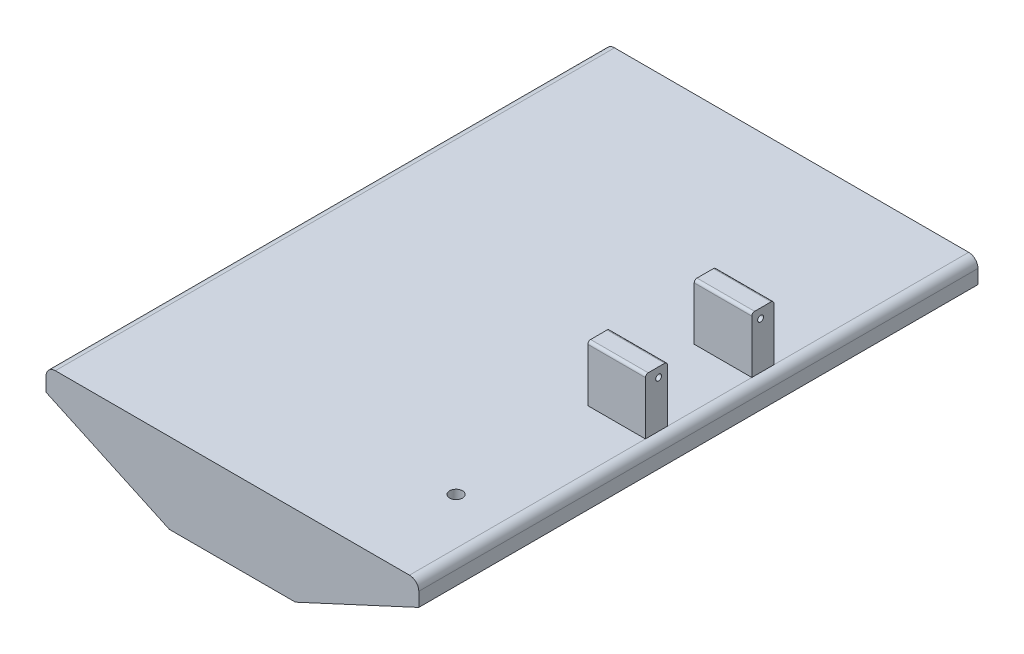
SolidWorks part; units mm, degrees
ref_plane "Front Plane" through (0, 0, 0) normal (0, 0, 1) x (1, 0, 0)
ref_plane "Top Plane" through (0, 0, 0) normal (0, 1, 0) x (1, 0, 0)
ref_plane "Right Plane" through (0, 0, 0) normal (1, 0, 0) x (0, 0, -1)
sketch "Sketch2" plane through (0, 0, 0) normal (0, 0, 1) x (1, 0, 0)
  line L0 (-50.8, -3.175) -> (-5.3359, -24.2247)
  line L1 (-50.8, 3.175) -> (50.8, 3.175)
  line L2 (-50.8, 3.175) -> (-50.8, -3.175)
  line L3 (-50.8, -3.175) -> (50.8, -3.175)
  line L4 (50.8, 3.175) -> (50.8, -3.175)
  line L5 (-50.8, 3.175) -> (50.8, -3.175) construction
  line L6 (-50.8, -3.175) -> (50.8, 3.175) construction
  line L7 (50.8, -3.175) -> (5.3359, -24.2247)
  arc A0 (-5.3359, -24.2247) -> (5.3359, -24.2247) centre (0, -12.7) ccw
  point P0 (0, 0)
  dimension "D3" = 25.4
  dimension "D1" = 101.6
  dimension "D2" = 6.35
  dimension "D4" = 12.7
extrude "Boss-Extrude1" add sketch "Sketch2" along normal blind 152.4 contours L0 A0 L7 L3 | L4 L1 L2 L3 region at (0, -10.9567, 0) region at (0, 0, 0)
sketch "Sketch3" plane through (0, 0, 152.4) normal (0, 0, 1) x (1, 0, 0)
  arc A0 (-5.3359, -24.2247) -> (5.3359, -24.2247) centre (0, -12.7) ccw construction
  arc A1 (-5.3359, -24.2247) -> (5.3359, -24.2247) centre (0, -12.7) ccw
  circle A2 centre (0, -12.7) radius 6.985
  dimension "D1" = 13.97
extrude "Cut-Extrude1" cut sketch "Sketch3" against normal through all from offset 6.35 contours A2 region at (0, -12.7, 152.4) offset against normal yes
sketch "Sketch4" plane through (0, 3.175, 0) normal (0, 1, 0) x (1, 0, 0)
  line L0 (-50.8, -152.4) -> (-50.8, 0) construction
  line L1 (-50.8, -57.15) -> (50.8, -57.15)
  line L2 (-50.8, -57.15) -> (-50.8, -95.25)
  line L3 (-50.8, -95.25) -> (50.8, -95.25)
  line L4 (50.8, -57.15) -> (50.8, -95.25)
  line L5 (50.8, -152.4) -> (50.8, 0) construction
  line L6 (0, 0) -> (0, -152.4) construction
  line L7 (-50.8, 0) -> (50.8, 0) construction
  line L8 (-50.8, -152.4) -> (50.8, -152.4) construction
  line L9 (50.8, -76.2) -> (-50.8, -76.2) construction
  point P16 (0, -76.2)
  dimension "D1" = 38.1
extrude "Cut-Extrude2" cut sketch "Sketch4" against normal through all from offset 6.35 offset against normal yes
fillet "Fillet4" radius 2.54 2 edges at (-50.8, 3.175, 76.2) (50.8, 3.175, 76.2)
sketch "Sketch5" plane through (0, 3.175, 0) normal (0, 1, 0) x (1, 0, 0)
  line L0 (48.26, -152.4) -> (48.26, 0) construction
  line L1 (48.26, -82.1) -> (32.56, -82.1)
  line L2 (48.26, -82.1) -> (48.26, -88.1)
  line L3 (48.26, -88.1) -> (32.56, -88.1)
  line L4 (32.56, -82.1) -> (32.56, -88.1)
  line L5 (48.26, -53.1) -> (32.56, -53.1)
  line L6 (48.26, -53.1) -> (48.26, -59.1)
  line L7 (48.26, -59.1) -> (32.56, -59.1)
  line L8 (32.56, -53.1) -> (32.56, -59.1)
  line L9 (-48.26, -152.4) -> (48.26, -152.4) construction
  dimension "D1" = 15.7
  dimension "D2" = 6
  dimension "D3" = 15.7
  dimension "D4" = 6
  dimension "D5" = 23
  dimension "D6" = 64.3
extrude "Boss-Extrude2" add sketch "Sketch5" along normal blind 15.24
sketch "Sketch6" plane through (32.56, 0, 0) normal (-1, 0, 0) x (0, 0, 1)
  line L0 (82.1, 18.415) -> (82.1, 3.175) construction
  line L2 (82.1, 3.175) -> (88.1, 3.175) construction
  line L3 (59.1, 10.795) -> (82.1, 10.795) construction
  line L4 (59.1, 18.415) -> (59.1, 3.175) construction
  line L5 (70.6, 10.795) -> (70.6, 3.175) construction
  line L6 (0, 3.175) -> (152.4, 3.175) construction
  circle A0 centre (84.495, 15.875) radius 0.8
  circle A1 centre (56.705, 15.875) radius 0.8
  dimension "D1" = 1.6
  dimension "D2" = 12.7
  dimension "D3" = 2.395
extrude "Cut-Extrude4" cut sketch "Sketch6" against normal through all contours A1 | A0
fillet "Fillet7" radius 0.762 2 edges at (40.41, 18.415, 88.1) (40.41, 18.415, 82.1)
fillet "Fillet8" radius 0.762 2 edges at (40.41, 18.415, 53.1) (40.41, 18.415, 59.1)
sketch "Sketch18" plane through (32.56, 0, 0) normal (-1, 0, 0) x (0, 0, 1)
  point P0 (84.495, 15.875)
  point P3 (56.705, 15.875)
hole_wizard "Tap Drill for M2 Tap3" positions "Sketch18" profile "Sketch19" hole size "M2" standard "ISO" end condition through all
sketch "Sketch19" plane through (32.56, 15.875, 84.495) normal (0, 1, 0) x (0, 0, 1)
  line L0 (0, 0) -> (0, 18.24)
  line L1 (0, 18.24) -> (0.8, 18.24)
  line L2 (0.8, 18.24) -> (0.8, 0)
  line L5 (0.8, 0) -> (0, 0)
  line L11 (0, -6.35) -> (0, 107.95) construction
  dimension "Thru Hole Dia." = 1.6
  dimension "Thru Hole Depth" = 18.24
sketch "Sketch20" plane through (0, 0, 0) normal (0, 0, -1) x (-1, 0, 0)
  line L0 (0, -12.7) -> (-3.4925, -18.7492) construction
  line L2 (0, -12.7) -> (3.4925, -18.7492) construction
  line L4 (-17.1621, -18.7492) -> (17.1621, -18.7492)
  line L5 (-50.8, -3.175) -> (-5.3359, -24.2247) construction
  line L6 (50.8, -3.175) -> (5.3359, -24.2247) construction
  line L7 (-50.8, -3.175) -> (-5.3359, -24.2247)
  line L8 (50.8, -3.175) -> (5.3359, -24.2247)
  circle A0 centre (0, -12.7) radius 6.985 construction
  circle A1 centre (0, -12.7) radius 6.985
  arc A2 (-5.3359, -24.2247) -> (5.3359, -24.2247) centre (0, -12.7) ccw construction
  arc A3 (-5.3359, -24.2247) -> (5.3359, -24.2247) centre (0, -12.7) ccw
  circle M4 centre (0, -12.7) radius 6.985
  line M10 (-50.8, -3.175) -> (-5.3359, -24.2247)
  arc M11 (-5.3359, -24.2247) -> (5.3359, -24.2247) centre (0, -12.7) ccw
  line M12 (5.3359, -24.2247) -> (50.8, -3.175)
  dimension "D1" = 60
extrude "Cut-Extrude5" cut sketch "Sketch20" against normal through all contours L4 M10 M11 M12 M4 | L4 M4 region at (0, -21.3175, 0) region at (0, -19.1257, 0)
fillet "Fillet9" radius 2.54 4 edges at (3.4925, -18.7492, 120.65) (-3.4925, -18.7492, 120.65) (-3.4925, -18.7492, 28.575) (3.4925, -18.7492, 28.575)
sketch "Sketch22" plane through (0, 0, 0) normal (0, 0, -1) x (-1, 0, 0)
  line L0 (0, -12.7) -> (0, 16.889) construction
  line L1 (-0.21, 0.9) -> (0.21, 0.9)
  circle A0 centre (0, -12.7) radius 16
  circle A1 centre (0, -12.7) radius 6.985 construction
  arc A2 (0.5094, 1.18) -> (2.08, 4.18) centre (4.6946, 0.9) cw
  arc A3 (0.21, 0.9) -> (0.5094, 1.18) centre (0.21, 1.2) ccw
  arc A4 (-0.21, 0.9) -> (-0.5094, 1.18) centre (-0.21, 1.2) cw
  arc A5 (-0.5094, 1.18) -> (-2.08, 4.18) centre (-4.6946, 0.9) ccw
  arc A6 (-2.08, 4.18) -> (2.08, 4.18) centre (0, -13.6994) cw
  point P7 (-0.5, 0.9)
  point P19 (0.5, 0.9)
  point P25 (0, 0.9)
  arc M3 (-6.4937, -15.2734) -> (6.4937, -15.2734) centre (0, -12.7) cw
  arc M4 (6.4937, -15.2734) -> (8.855, -18.7492) centre (8.855, -16.2092) ccw
  line M5 (8.855, -18.7492) -> (17.1621, -18.7492)
  line M9 (48.26, 3.175) -> (-48.26, 3.175)
  line M13 (-17.1621, -18.7492) -> (-8.855, -18.7492)
  arc M14 (-8.855, -18.7492) -> (-6.4937, -15.2734) centre (-8.855, -16.2092) ccw
  dimension "D1" = 32
  dimension "D6" = 0.3
  dimension "D7" = 18
  dimension "D2" = 0.5
  dimension "D3" = 1.58
  dimension "D4" = 3.28
  dimension "D5" = 13.6
extrude "Boss-Extrude3" add sketch "Sketch22" against normal up to surface (57.15 mm away) contours L0 A0 A2 A3 L1 M3 M4 M5 M9 | L0 A0 M5 M4 M3 | A0 L0 M3 M14 M13 | L0 L1 A4 A5 A0 M3 M9 M13 M14 | L0 L1 A3 A2 M9 | L1 L0 A5 A4 M9 region at (8.6235, -7.721, 0) region at (0, -18.5871, 0) region at (-8.6235, -7.721, 0) region at (0.3846, 2.2253, 0) region at (-0.3846, 2.2253, 0) up to face at (0, -12.9482, 57.15)
extrude "Cut-Extrude6" cut sketch "Sketch22<3>" against normal up to surface (57.15 mm away) contours L0 A0 A2 A6 | L0 L1 A3 A2 M9 | L1 L0 A5 A4 M9 | A0 L0 A6 A5 | L0 A0 A5 M9 | L0 A2 A0 M9 region at (0.3846, 2.2253, 0) region at (-0.3846, 2.2253, 0) region at (0.5578, 3.2311, 0) region at (-0.5578, 3.2311, 0) region at (0.8269, 3.8175, 0) region at (-0.8269, 3.8175, 0) up to face at (0, -15.2163, 57.15)
sketch "Sketch22<3>" plane through (0, 0, 0) normal (0, 0, -1) x (-1, 0, 0) same geometry as "Sketch22"
pattern_circular "CirPattern1" count 30 over 360 about axis through (0, -12.7, 102.3165) along (0, 0, -1) of "Cut-Extrude6" reverse direction yes
sketch "Sketch23" plane through (0, 0, 0) normal (0, 0, -1) x (-1, 0, 0)
  arc A0 (6.4937, -15.2734) -> (-6.4937, -15.2734) centre (0, -12.7) ccw construction
  arc A1 (6.4937, -15.2734) -> (-6.4937, -15.2734) centre (0, -12.7) ccw
  circle A2 centre (0, -12.7) radius 6.985
  point P4 (0, 0)
extrude "Cut-Extrude7" cut sketch "Sketch23" against normal up to surface (57.15 mm away) contours A1 A2 region at (0, -12.7, 0) up to face at (17.8003, -10.9681, 57.15)
sketch "Sketch26" plane through (0, 0, 0) normal (0, 0, -1) x (-1, 0, 0)
  line L0 (50.8, 0.635) -> (50.8, -3.175) construction
  line L1 (48.26, 3.175) -> (-48.26, 3.175) construction
  line L2 (-50.8, 0.635) -> (-50.8, -3.175) construction
  line L3 (-6.0868, 3.175) -> (-48.26, 3.175) construction
  line L4 (50.8, 0.635) -> (50.8, -3.175)
  line L5 (-17.1621, -18.7492) -> (-8.855, -18.7492)
  line L6 (8.855, -18.7492) -> (17.1621, -18.7492)
  line L7 (17.1621, -18.7492) -> (50.8, -3.175)
  line L8 (50.8, -3.175) -> (-50.8, -3.175)
  line L9 (-50.8, -3.175) -> (-17.1621, -18.7492)
  line L10 (-17.1621, -18.7492) -> (-8.855, -18.7492)
  line L11 (8.855, -18.7492) -> (17.1621, -18.7492)
  line L12 (17.1621, -18.7492) -> (50.8, -3.175)
  line L14 (-50.8, -3.175) -> (-17.1621, -18.7492)
  line L15 (48.26, 3.175) -> (-48.26, 3.175)
  line L16 (-50.8, 0.635) -> (-50.8, -3.175)
  line L17 (-6.0868, 3.175) -> (-48.26, 3.175)
  arc A0 (50.8, 0.635) -> (48.26, 3.175) centre (48.26, 0.635) ccw construction
  arc A1 (-48.26, 3.175) -> (-50.8, 0.635) centre (-48.26, 0.635) ccw construction
  arc A2 (50.8, 0.635) -> (48.26, 3.175) centre (48.26, 0.635) ccw
  arc A3 (-8.855, -18.7492) -> (-6.4937, -15.2734) centre (-8.855, -16.2092) ccw
  arc A4 (6.4937, -15.2734) -> (-6.4937, -15.2734) centre (0, -12.7) ccw
  arc A5 (6.4937, -15.2734) -> (8.855, -18.7492) centre (8.855, -16.2092) ccw
  arc A6 (-8.855, -18.7492) -> (-6.4937, -15.2734) centre (-8.855, -16.2092) ccw
  arc A7 (6.4937, -15.2734) -> (-6.4937, -15.2734) centre (0, -12.7) ccw
  arc A8 (6.4937, -15.2734) -> (8.855, -18.7492) centre (8.855, -16.2092) ccw
  arc A9 (-48.26, 3.175) -> (-50.8, 0.635) centre (-48.26, 0.635) ccw
  arc M9 (-15.8892, -18.7492) -> (-16.5675, -16.5289) centre (0.9505, -12.3912) cw
  arc M10 (-16.5675, -16.5289) -> (-16.5701, -16.533) centre (-13.0348, -18.7904) ccw
  arc M11 (-16.5701, -16.533) -> (-16.6341, -16.2357) centre (0.9939, -12.5955) cw
  arc M12 (-16.6341, -16.2357) -> (-16.6966, -15.938) centre (0.9505, -12.3912) cw
  arc M13 (-16.6966, -15.938) -> (-16.6925, -15.9407) centre (-14.3851, -12.4378) ccw
  arc M14 (-16.6925, -15.9407) -> (-17.0015, -13.0007) centre (0.9939, -12.5955) cw
  arc M15 (-17.0015, -13.0007) -> (-17.0049, -13.0042) centre (-14.0162, -15.9473) ccw
  arc M16 (-17.0049, -13.0042) -> (-17.0058, -12.7) centre (0.9939, -12.8045) cw
  arc M17 (-17.0058, -12.7) -> (-17.0049, -12.3958) centre (0.9939, -12.5955) cw
  arc M18 (-17.0049, -12.3958) -> (-17.0015, -12.3993) centre (-14.0162, -9.4527) ccw
  arc M19 (-17.0015, -12.3993) -> (-16.6925, -9.4593) centre (0.9939, -12.8045) cw
  arc M20 (-16.6925, -9.4593) -> (-16.6966, -9.462) centre (-14.3851, -12.9622) ccw
  arc M21 (-16.6966, -9.462) -> (-16.6341, -9.1643) centre (0.9505, -13.0088) cw
  arc M22 (-16.6341, -9.1643) -> (-16.5701, -8.867) centre (0.9939, -12.8045) cw
  arc M23 (-16.5701, -8.867) -> (-16.5675, -8.8711) centre (-13.0348, -6.6096) ccw
  arc M24 (-16.5675, -8.8711) -> (-15.6539, -6.0595) centre (0.9505, -13.0088) cw
  arc M25 (-15.6539, -6.0595) -> (-15.6585, -6.0613) centre (-14.1252, -9.9656) ccw
  arc M26 (-15.6585, -6.0613) -> (-15.5355, -5.7831) centre (0.8655, -13.1997) cw
  arc M27 (-15.5355, -5.7831) -> (-15.4111, -5.5056) centre (0.9505, -13.0088) cw
  arc M28 (-15.4111, -5.5056) -> (-15.4093, -5.5102) centre (-11.4837, -4.0326) ccw
  arc M29 (-15.4093, -5.5102) -> (-13.9312, -2.95) centre (0.8655, -13.1997) cw
  arc M30 (-13.9312, -2.95) -> (-13.9361, -2.9508) centre (-13.248, -7.0886) ccw
  arc M31 (-13.9361, -2.9508) -> (-13.7579, -2.7043) centre (0.7427, -13.3687) cw
  arc M32 (-13.7579, -2.7043) -> (-13.5785, -2.4587) centre (0.8655, -13.1997) cw
  arc M33 (-13.5785, -2.4587) -> (-13.5778, -2.4635) centre (-9.4307, -1.8344) ccw
  arc M34 (-13.5778, -2.4635) -> (-11.5997, -0.2666) centre (0.7427, -13.3687) cw
  arc M35 (-11.5997, -0.2666) -> (-11.6046, -0.2664) centre (-11.7919, -4.4568) ccw
  arc M36 (-11.6046, -0.2664) -> (-11.3791, -0.0623) centre (0.5874, -13.5085) cw
  arc M37 (-11.3791, -0.0623) -> (-11.1525, 0.1407) centre (0.7427, -13.3687) cw
  arc M38 (-11.1525, 0.1407) -> (-11.1528, 0.1358) centre (-6.9655, -0.1111) ccw
  arc M39 (-11.1528, 0.1358) -> (-8.7611, 1.8734) centre (0.5874, -13.5085) cw
  arc M40 (-8.7611, 1.8734) -> (-8.7659, 1.8746) centre (-9.8203, -2.1852) ccw
  arc M41 (-8.7659, 1.8746) -> (-8.5029, 2.0274) centre (0.4065, -13.613) cw
  arc M42 (-8.5029, 2.0274) -> (-8.2391, 2.1788) centre (0.5874, -13.5085) cw
  arc M43 (-8.2391, 2.1788) -> (-8.2404, 2.1741) centre (-4.1959, 1.062) ccw
  arc M44 (-8.2404, 2.1741) -> (-6.0868, 3.175) centre (0.4065, -13.613) cw
  line M45 (-6.0868, 3.175) -> (-48.26, 3.175)
  arc M46 (-48.26, 3.175) -> (-50.8, 0.635) centre (-48.26, 0.635) ccw
  line M47 (-50.8, 0.635) -> (-50.8, -3.175)
  line M48 (-50.8, -3.175) -> (-17.1621, -18.7492)
  line M49 (-17.1621, -18.7492) -> (-15.8892, -18.7492)
  dimension "D1" = 0
extrude "Boss-Extrude7" add sketch "Sketch26" against normal up to surface (57.15 mm away) contours M49 M9 M10 M11 M12 M13 M14 M15 M16 M17 M18 M19 M20 M21 M22 M23 M24 M25 M26 M27 M28 M29 M30 M31 M32 M33 M34 M35 M36 M37 M38 M39 M40 M41 M42 M43 M44 M45 M46 M47 M48 | A7 A8 L11 L12 L4 A2 L15 L10 A6 M44 M43 M42 M41 M40 M39 M38 M37 M36 M35 M34 M33 M32 M31 M30 M29 M28 M27 M26 M25 M24 M23 M22 M21 M20 M19 M18 M17 M16 M15 M14 M13 M12 M11 M10 M9 region at (-19.7867, -0.0747, 0) region at (-12.2622, -9.4518, 0) region at (27.7827, -8.3688, 0) region at (30.6968, 0.0872, 0) up to face at (17.8003, -10.9681, 57.15)
sketch "Sketch27" plane through (0, 3.175, 0) normal (0, 1, 0) x (1, 0, 0)
  line L0 (48.26, -152.4) -> (48.26, -88.1) construction
  line L1 (-48.26, -152.4) -> (48.26, -152.4) construction
  circle A0 centre (35.56, -127) radius 1.75
  dimension "D1" = 3.5
  dimension "D2" = 12.7
  dimension "D3" = 25.4
extrude "Cut-Extrude8" cut sketch "Sketch27" against normal through all
